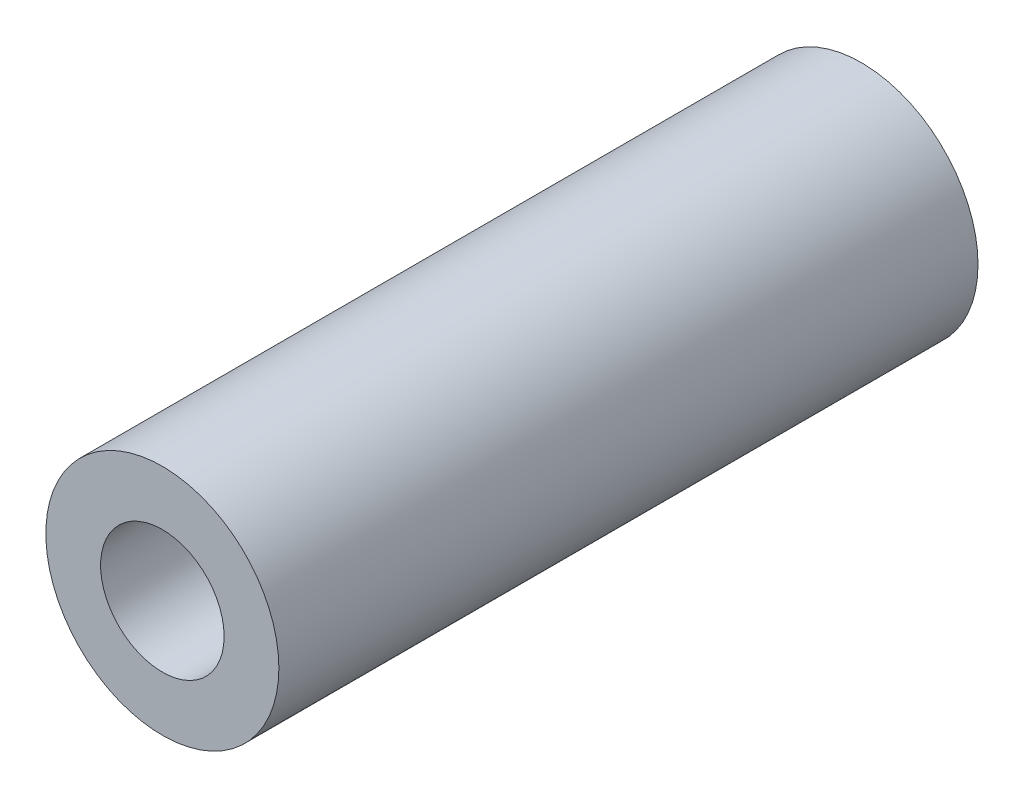
SolidWorks part; units mm, degrees
ref_plane "Front Plane" through (0, 0, 0) normal (0, 0, 1) x (1, 0, 0)
ref_plane "Top Plane" through (0, 0, 0) normal (0, 1, 0) x (1, 0, 0)
ref_plane "Right Plane" through (0, 0, 0) normal (1, 0, 0) x (0, 0, -1)
sketch "Cross Section Sketch" plane through (0, 0, 0) normal (0, 0, 1) x (1, 0, 0)
  circle A0 centre (0, 0) radius 5
  circle A1 centre (0, 0) radius 2.65
  dimension "OD" = 10
  dimension "ID" = 5.3
extrude "Extrude Length" add sketch "Cross Section Sketch" along normal mid plane 30
